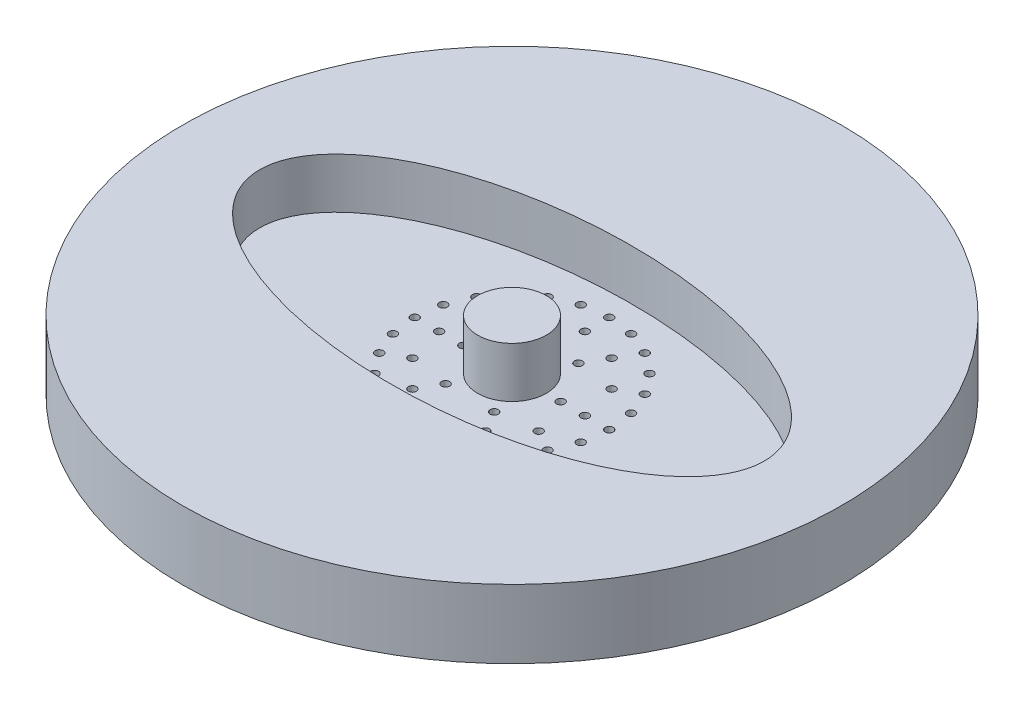
SolidWorks part; units mm, degrees
ref_plane "Front Plane" through (0, 0, 0) normal (0, 0, 1) x (1, 0, 0)
ref_plane "Top Plane" through (0, 0, 0) normal (0, 1, 0) x (1, 0, 0)
ref_plane "Right Plane" through (0, 0, 0) normal (1, 0, 0) x (0, 0, -1)
ref_axis "Axial" through (0, 0.508, 0) along (0, -1, 0)
ref_plane "Bottom Plane" through (0, -12.7, 0) normal (0, 1, 0) x (1, 0, 0)
sketch "Sketch1" plane through (0, 0, 0) normal (0, 1, 0) x (1, 0, 0)
  circle A0 centre (0, 0) radius 60.96
  dimension "D1" = 121.92
extrude "Billet" add sketch "Sketch1" against normal blind 12.7
sketch "Sketch4" plane through (0, -12.7, 0) normal (0, 1, 0) x (1, 0, 0)
  line L0 (0, 37.2675) -> (0, -28.2573) construction
  line L1 (-38.2015, 0) -> (37.6086, 0) construction
  circle A0 centre (8.9916, 0) radius 0.7493
  circle A1 centre (13.4874, 0) radius 0.7493
  circle A2 centre (17.9832, 0) radius 0.7493
  dimension "D1" = 1.4986
  dimension "D3" = 4.4958
  dimension "D4" = 4.4958
  dimension "D2" = 8.9916
extrude "First Kerosene Outlet" cut sketch "Sketch4" along normal through all and the other way through all
sketch "Sketch15" plane through (0, -12.7, 0) normal (0, 1, 0) x (1, 0, 0)
  circle A0 centre (0, 0) radius 57.15
  circle A1 centre (0, 0) radius 59.69
  dimension "D1" = 114.3
  dimension "D2" = 119.38
sketch "Sketch16" plane through (0, 0, 0) normal (0, 1, 0) x (1, 0, 0)
  circle A0 centre (0, 0) radius 59.69
  circle A1 centre (0, 0) radius 57.15
  dimension "D1" = 119.38
  dimension "D2" = 114.3
pattern_circular "Primary Holes" count 6 over 360 about axis through (0, 0.508, 0) along (0, -1, 0) of "First Kerosene Outlet"
pattern_circular "Second ring" count 12 over 360 about axis through (0, 0.508, 0) along (0, -1, 0) skipping 2, 4, 6, 8, 10 of face at (13.4874, 0, 0.7493)
pattern_circular "Third Ring" count 24 over 360 about axis through (0, 0.508, 0) along (0, -1, 0) skipping 4, 8, 12, 16, 20 of face at (17.9832, 0, 0.7493)
sketch "Sketch18" plane through (0, 0, 0) normal (0, 1, 0) x (1, 0, 0)
  line L0 (-47.0718, 0) -> (54.8652, 0) construction
  line L1 (0, 40.3695) -> (0, -40.0578) construction
  ellipse E0 centre (0, 0) end of major axis (-46.675, 0) minor radius 22.225
  dimension "D1" = 46.675
  dimension "D2" = 22.225
extrude "Kerosene Well" cut sketch "Sketch18" against normal blind 9.3218
sketch "Sketch17" plane through (0, 0, 0) normal (0, 1, 0) x (1, 0, 0)
  circle A0 centre (0, 0) radius 6.35
  dimension "D1" = 12.7
extrude "Boss-Extrude1" add sketch "Sketch17" along normal blind 2.54 and the other way up to next
sketch "Sketch21" plane through (0, 2.54, 0) normal (0, 1, 0) x (1, 0, 0)
  circle A0 centre (0, 0) radius 6.35
  dimension "D1" = 12.7
extrude "Cut-Extrude1" cut sketch "Sketch21" against normal blind 2.54
sketch "Sketch20" plane through (0, 0, 0) normal (0, 1, 0) x (1, 0, 0)
  line L0 (0, 68.1298) -> (0, -73.4056) construction
  line L1 (-6.985, 0) -> (6.985, 0) construction
  circle A0 centre (0, 25.4) radius 1.1906
  circle A1 centre (0, -25.4) radius 1.1906
  circle A2 centre (0, 50.8) radius 1.1906
  circle A3 centre (0, -50.8) radius 1.1906
  dimension "D1" = 2.3813
  dimension "D3" = 2.3813
  dimension "D2" = 25.4
  dimension "D4" = 50.8
